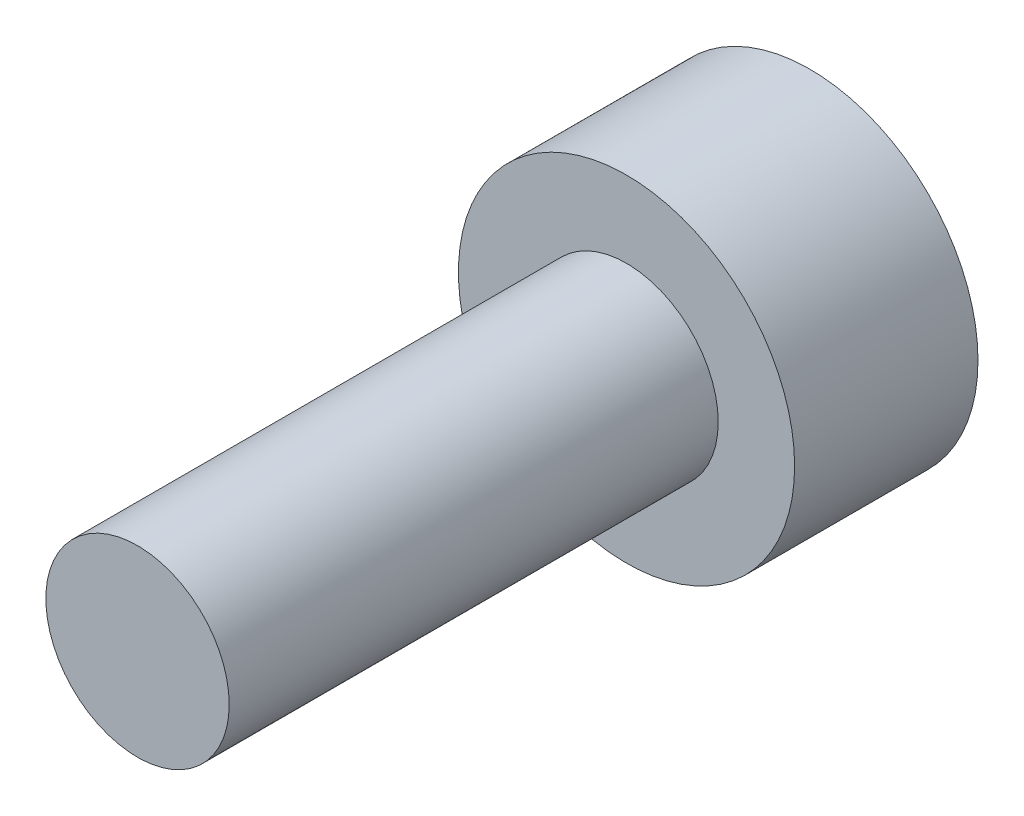
SolidWorks part; units mm, degrees
ref_plane "Front Plane" through (0, 0, 0) normal (0, 0, 1) x (1, 0, 0)
ref_plane "Top Plane" through (0, 0, 0) normal (0, 1, 0) x (1, 0, 0)
ref_plane "Right Plane" through (0, 0, 0) normal (1, 0, 0) x (0, 0, -1)
sketch "S01 - Head" plane through (0, 0, 0) normal (0, 0, 1) x (1, 0, 0)
  circle A0 centre (0, 0) radius 2.75
  dimension "D1" = 5.5
extrude "01 - Head" add sketch "S01 - Head" along normal blind 3 from offset 3 offset against normal yes
sketch "S02 - Nominal shank" plane through (0, 0, 0) normal (0, 0, 1) x (1, 0, 0)
  circle A0 centre (0, 0) radius 1.5
  dimension "D1" = 3
extrude "02 - Nominal shank" add sketch "S02 - Nominal shank" along normal blind 8
sketch "S03 - Hex key socket" plane through (0, 0, 0) normal (0, 0, 1) x (1, 0, 0)
  line L0 (1.4434, 0) -> (0.7217, 1.25)
  line L1 (0.7217, 1.25) -> (-0.7217, 1.25)
  line L2 (-0.7217, 1.25) -> (-1.4434, 0)
  line L3 (-1.4434, 0) -> (-0.7217, -1.25)
  line L4 (-0.7217, -1.25) -> (0.7217, -1.25)
  line L5 (0.7217, -1.25) -> (1.4434, 0)
  dimension "D1" = 0.7217
  dimension "D2" = 1.4434
  dimension "D3" = 0.7217
  dimension "D4" = 1.4434
  dimension "D5" = 1.25
  dimension "D6" = 1.25
extrude "03 - Hex key socket" cut sketch "S03 - Hex key socket" along normal blind 1.75 from offset 3.1 offset against normal yes
